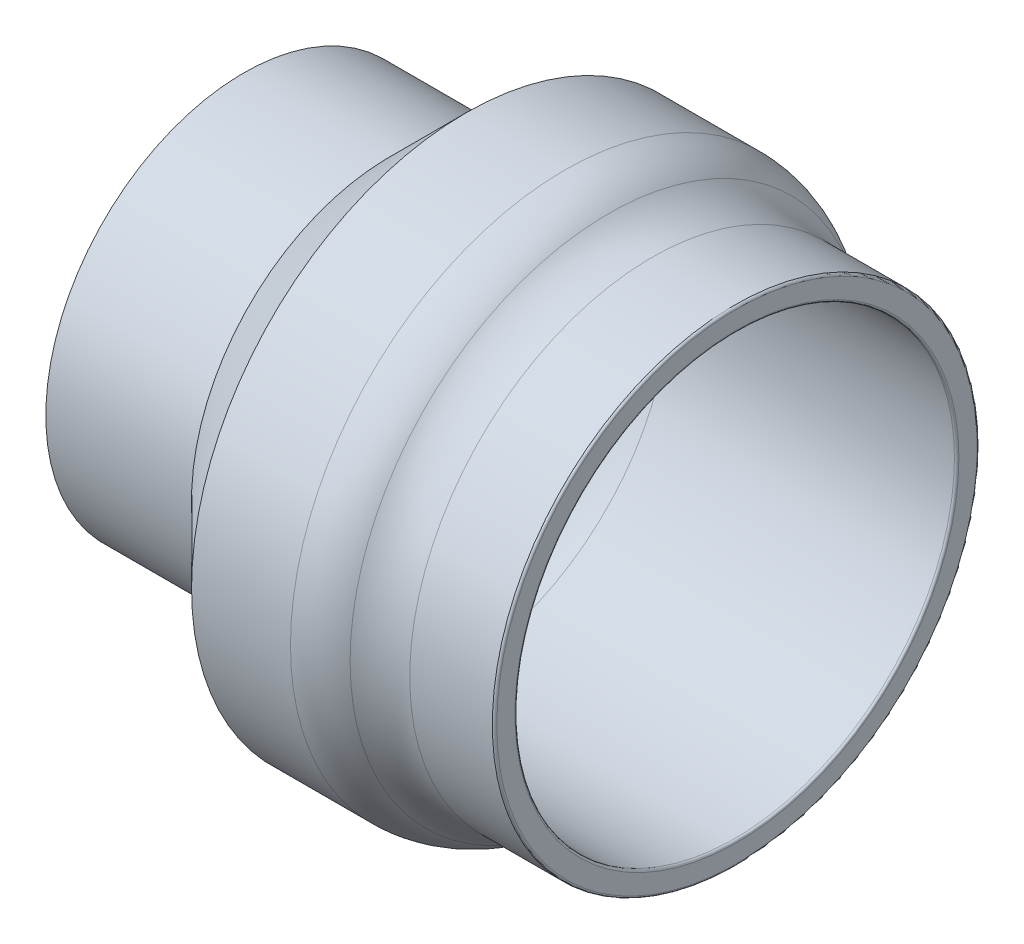
SolidWorks part; units mm, degrees
material "moto_Rubber"
ref_plane "Front Plane" through (0, 0, 0) normal (0, 0, 1) x (1, 0, 0)
ref_plane "Top Plane" through (0, 0, 0) normal (0, 1, 0) x (1, 0, 0)
ref_plane "Right Plane" through (0, 0, 0) normal (1, 0, 0) x (0, 0, -1)
sketch "Sketch1" plane through (0, 0, 0) normal (1, 0, 0) x (0, 0, -1)
  circle A0 centre (0, 0) radius 8.825
  circle A1 centre (0, 0) radius 7.825
  dimension "D1" = 17.65
  dimension "D2" = 1
extrude "Boss-Extrude1" add sketch "Sketch1" along normal blind 10
sketch "Sketch2" plane through (10, 0, 0) normal (1, 0, 0) x (0, 0, -1)
  circle A0 centre (0, 0) radius 12.24
  circle A1 centre (0, 0) radius 7.825
  dimension "D1" = 24.48
extrude "Boss-Extrude2" add sketch "Sketch2" along normal blind 12
chamfer "Chamfer1" distance 3.5 angle 45 1 edges at (10, 0, -8.825)
sketch "Sketch3" plane through (22, 0, 0) normal (1, 0, 0) x (0, 0, -1)
  circle A0 centre (0, 0) radius 9.8
  dimension "D1" = 19.6
extrude "Cut-Extrude1" cut sketch "Sketch3" against normal blind 12
chamfer "Chamfer2" distance 4 angle 45 1 edges at (10, 0, -7.825)
fillet "Fillet1" radius 3 2 edges at (6, 0, -7.825) (7.975, 0, -9.8)
sketch "Sketch4" plane through (22, 0, 0) normal (1, 0, 0) x (0, 0, -1)
  circle A0 centre (0, 0) radius 10.8101
  circle A1 centre (0, 0) radius 12.8101
  dimension "D1" = 2
extrude "Cut-Extrude2" cut sketch "Sketch4" against normal blind 7
chamfer "Chamfer3" distance 2 angle 45 1 edges at (15, 0, -10.8101)
fillet "Fillet2" radius 3 1 edges at (15.5701, 0, 12.24)
fillet "Fillet3" radius 3 1 edges at (17, 0, -10.8101)
fillet "Fillet4" radius 0.1 2 edges at (22, 0, -9.8) (22, 0, -10.8101)
